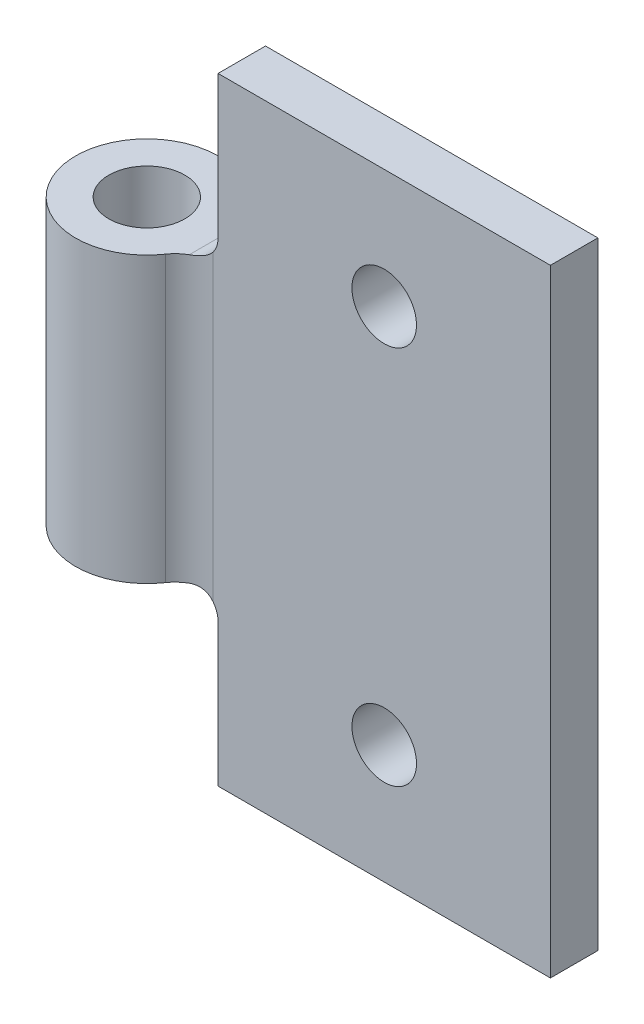
SolidWorks part; units mm, degrees
ref_plane "Front Plane" through (0, 0, 0) normal (0, 0, 1) x (1, 0, 0)
ref_plane "Top Plane" through (0, 0, 0) normal (0, 1, 0) x (1, 0, 0)
ref_plane "Right Plane" through (0, 0, 0) normal (1, 0, 0) x (0, 0, -1)
sketch "Sketch1" plane through (0, 0, 0) normal (0, 0, 1) x (1, 0, 0)
  line L0 (0, 0) -> (22.225, 0)
  line L1 (22.225, 0) -> (22.225, 41.275)
  line L2 (22.225, 41.275) -> (0, 41.275)
  line L3 (0, 41.275) -> (0, 31.7373)
  line L4 (-1.5875, 30.1498) -> (-6.35, 30.1498)
  line L5 (-6.35, 30.1498) -> (-6.35, 11.1252)
  line L6 (-6.35, 11.1252) -> (-1.5875, 11.1252)
  line L7 (0, 9.5377) -> (0, 0)
  line L8 (-6.35, 20.6375) -> (22.225, 20.6375) construction
  line L9 (11.1125, 7.9375) -> (11.1125, 20.6375) construction
  circle A0 centre (11.1125, 7.9375) radius 2.1593
  circle A1 centre (11.1125, 33.3375) radius 2.1593
  arc A2 (-1.5875, 11.1252) -> (0, 9.5377) centre (-1.5875, 9.5377) cw
  arc A3 (0, 31.7373) -> (-1.5875, 30.1498) centre (-1.5875, 31.7373) cw
  point P18 (0, 11.1252)
  point P21 (0, 30.1498)
  dimension "D6" = 1.5875
  dimension "D1" = 22.225
  dimension "D2" = 11.1252
  dimension "D3" = 11.1252
  dimension "D4" = 41.275
  dimension "D5" = 6.35
extrude "Boss-Extrude1" add sketch "Sketch1" along normal mid plane 3.175
ref_plane "Plane1" through (0, 30.1498, 0) normal (0, 1, 0) x (-1, 0, 0)
sketch "Sketch2" plane through (0, 30.1498, 0) normal (0, 1, 0) x (-1, 0, 0)
  line L0 (6.35, 0) -> (11.1125, 0) construction
  line L1 (6.35, 1.5875) -> (6.35, -1.5875) construction
  circle A0 centre (6.35, 0) radius 4.7625
  dimension "D1" = 4.7625
extrude "Boss-Extrude2" add sketch "Sketch2" against normal up to vertex (19.0246 mm away) up to point (-6.35, 11.1252, 1.5875)
sketch "Sketch3" plane through (0, 30.1498, 0) normal (0, 1, 0) x (-1, 0, 0)
  circle A0 centre (6.35, 0) radius 2.54
extrude "Cut-Extrude1" cut sketch "Sketch3" against normal through all
fillet "Fillet1" radius 2.54 2 edges at (-1.8599, 20.6375, -1.5875) (-1.8599, 20.6375, 1.5875)
